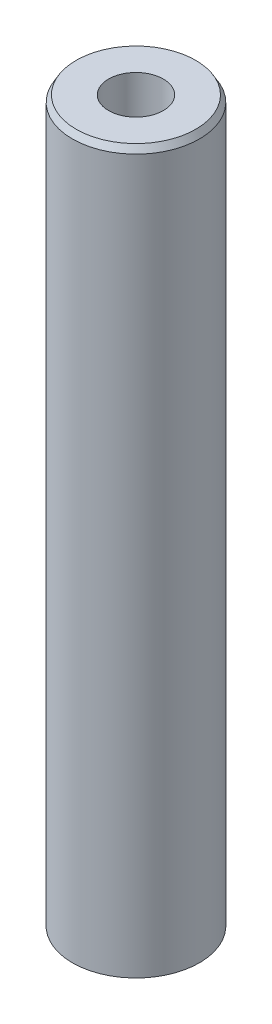
SolidWorks part; units mm, degrees
ref_plane "Front Plane" through (0, 0, 0) normal (0, 0, 1) x (1, 0, 0)
ref_plane "Top Plane" through (0, 0, 0) normal (0, 1, 0) x (1, 0, 0)
ref_plane "Right Plane" through (0, 0, 0) normal (1, 0, 0) x (0, 0, -1)
sketch "Sketch1" plane through (0, 0, 0) normal (0, 1, 0) x (1, 0, 0)
  circle A0 centre (0, 0) radius 47.5
  dimension "SHAFT_OD" = 95
extrude "Boss-Extrude1" add sketch "Sketch1" along normal blind 541.1529
sketch "Sketch2" plane through (0, 0, 0) normal (0, 1, 0) x (1, 0, 0)
  circle A0 centre (0, 0) radius 20.471
  dimension "BORE_D" = 40.942
extrude "Cut-Extrude1" cut sketch "Sketch2" along normal through all
chamfer "Chamfer1" distance 4.8626 angle 30 2 edges at (0, 541.1529, 47.5) (0, 0, 47.5) first distance on face at (0, 541.1529, 47.5) first distance on face at (0, 0, 20.471)
